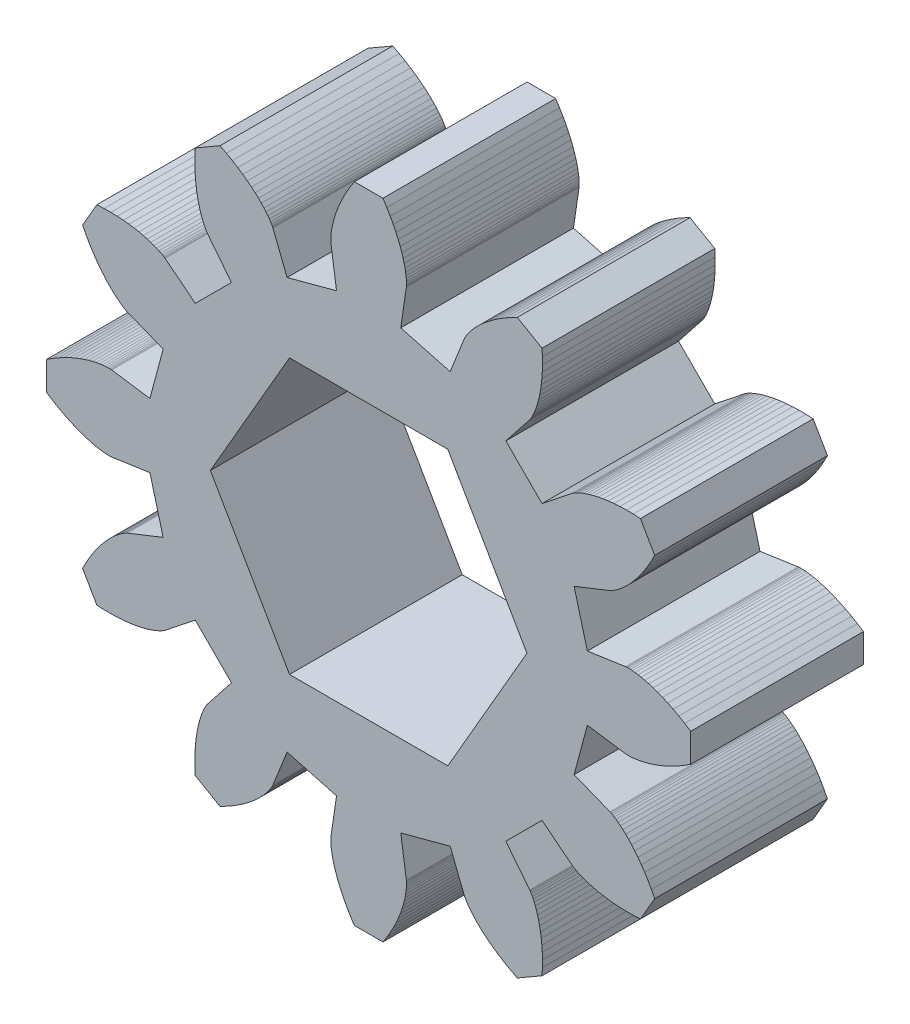
SolidWorks part; units mm, degrees
ref_plane "Front Plane" through (0, 0, 0) normal (0, 0, 1) x (1, 0, 0)
ref_plane "Top Plane" through (0, 0, 0) normal (0, 1, 0) x (1, 0, 0)
ref_plane "Right Plane" through (0, 0, 0) normal (1, 0, 0) x (0, 0, -1)
sketch "Model" plane through (0, 0, 0) normal (0, 0, 1) x (1, 0, 0)
  line L0 (7.5985, 1.1158) -> (8.9253, 1.3107)
  line L1 (8.9253, 1.3107) -> (8.932, 1.3115)
  line L2 (8.932, 1.3115) -> (8.9523, 1.3132)
  line L3 (8.9523, 1.3132) -> (8.986, 1.3148)
  line L4 (8.986, 1.3148) -> (9.0334, 1.3152)
  line L5 (9.0334, 1.3152) -> (9.0943, 1.3135)
  line L6 (9.0943, 1.3135) -> (9.1685, 1.3084)
  line L7 (9.1685, 1.3084) -> (9.2559, 1.2991)
  line L8 (9.2559, 1.2991) -> (9.3563, 1.2844)
  line L9 (9.3563, 1.2844) -> (9.4694, 1.2634)
  line L10 (9.4694, 1.2634) -> (9.5947, 1.2351)
  line L11 (9.5947, 1.2351) -> (9.732, 1.1984)
  line L12 (9.732, 1.1984) -> (9.8806, 1.1524)
  line L13 (9.8806, 1.1524) -> (10.0401, 1.0963)
  line L14 (10.0401, 1.0963) -> (10.2099, 1.029)
  line L15 (10.2099, 1.029) -> (10.3894, 0.9497)
  line L16 (10.3894, 0.9497) -> (10.5778, 0.8576)
  line L17 (10.5778, 0.8576) -> (10.7744, 0.7519)
  line L18 (10.7744, 0.7519) -> (10.9784, 0.6318)
  line L19 (10.9784, 0.6318) -> (11.189, 0.4965)
  line L20 (11.189, 0.4965) -> (11.189, -0.4965)
  line L21 (11.189, -0.4965) -> (10.9784, -0.6318)
  line L22 (10.9784, -0.6318) -> (10.7744, -0.7519)
  line L23 (10.7744, -0.7519) -> (10.5778, -0.8576)
  line L24 (10.5778, -0.8576) -> (10.3894, -0.9497)
  line L25 (10.3894, -0.9497) -> (10.2099, -1.029)
  line L26 (10.2099, -1.029) -> (10.0401, -1.0963)
  line L27 (10.0401, -1.0963) -> (9.8806, -1.1524)
  line L28 (9.8806, -1.1524) -> (9.732, -1.1984)
  line L29 (9.732, -1.1984) -> (9.5947, -1.2351)
  line L30 (9.5947, -1.2351) -> (9.4694, -1.2634)
  line L31 (9.4694, -1.2634) -> (9.3563, -1.2844)
  line L32 (9.3563, -1.2844) -> (9.2559, -1.2991)
  line L33 (9.2559, -1.2991) -> (9.1685, -1.3084)
  line L34 (9.1685, -1.3084) -> (9.0943, -1.3135)
  line L35 (9.0943, -1.3135) -> (9.0334, -1.3152)
  line L36 (9.0334, -1.3152) -> (8.986, -1.3148)
  line L37 (8.986, -1.3148) -> (8.9523, -1.3132)
  line L38 (8.9523, -1.3132) -> (8.932, -1.3115)
  line L39 (8.932, -1.3115) -> (8.9253, -1.3107)
  line L40 (8.9253, -1.3107) -> (7.5985, -1.1158)
  line L41 (7.5985, -1.1158) -> (7.1384, -2.8329)
  line L42 (7.1384, -2.8329) -> (8.3849, -3.3276)
  line L43 (8.3849, -3.3276) -> (8.3911, -3.3303)
  line L44 (8.3911, -3.3303) -> (8.4095, -3.3389)
  line L45 (8.4095, -3.3389) -> (8.4396, -3.3544)
  line L46 (8.4396, -3.3544) -> (8.4808, -3.3777)
  line L47 (8.4808, -3.3777) -> (8.5326, -3.4096)
  line L48 (8.5326, -3.4096) -> (8.5944, -3.4511)
  line L49 (8.5944, -3.4511) -> (8.6654, -3.5029)
  line L50 (8.6654, -3.5029) -> (8.745, -3.5658)
  line L51 (8.745, -3.5658) -> (8.8324, -3.6406)
  line L52 (8.8324, -3.6406) -> (8.9268, -3.7278)
  line L53 (8.9268, -3.7278) -> (9.0273, -3.8282)
  line L54 (9.0273, -3.8282) -> (9.1331, -3.9423)
  line L55 (9.1331, -3.9423) -> (9.2431, -4.0707)
  line L56 (9.2431, -4.0707) -> (9.3566, -4.2138)
  line L57 (9.3566, -4.2138) -> (9.4723, -4.3722)
  line L58 (9.4723, -4.3722) -> (9.5894, -4.5462)
  line L59 (9.5894, -4.5462) -> (9.7068, -4.736)
  line L60 (9.7068, -4.736) -> (9.8235, -4.9421)
  line L61 (9.8235, -4.9421) -> (9.9382, -5.1645)
  line L62 (9.9382, -5.1645) -> (9.4417, -6.0245)
  line L63 (9.4417, -6.0245) -> (9.1917, -6.0363)
  line L64 (9.1917, -6.0363) -> (8.9549, -6.0384)
  line L65 (8.9549, -6.0384) -> (8.7318, -6.0316)
  line L66 (8.7318, -6.0316) -> (8.5226, -6.0172)
  line L67 (8.5226, -6.0172) -> (8.3276, -5.9961)
  line L68 (8.3276, -5.9961) -> (8.1469, -5.9695)
  line L69 (8.1469, -5.9695) -> (7.9807, -5.9383)
  line L70 (7.9807, -5.9383) -> (7.829, -5.9038)
  line L71 (7.829, -5.9038) -> (7.6918, -5.867)
  line L72 (7.6918, -5.867) -> (7.569, -5.8288)
  line L73 (7.569, -5.8288) -> (7.4606, -5.7905)
  line L74 (7.4606, -5.7905) -> (7.3663, -5.753)
  line L75 (7.3663, -5.753) -> (7.2859, -5.7174)
  line L76 (7.2859, -5.7174) -> (7.2191, -5.6846)
  line L77 (7.2191, -5.6846) -> (7.1655, -5.6557)
  line L78 (7.1655, -5.6557) -> (7.1247, -5.6317)
  line L79 (7.1247, -5.6317) -> (7.0963, -5.6134)
  line L80 (7.0963, -5.6134) -> (7.0796, -5.6018)
  line L81 (7.0796, -5.6018) -> (7.0742, -5.5977)
  line L82 (7.0742, -5.5977) -> (6.0226, -4.7656)
  line L83 (6.0226, -4.7656) -> (4.7656, -6.0226)
  line L84 (4.7656, -6.0226) -> (5.5977, -7.0742)
  line L85 (5.5977, -7.0742) -> (5.6018, -7.0796)
  line L86 (5.6018, -7.0796) -> (5.6134, -7.0963)
  line L87 (5.6134, -7.0963) -> (5.6317, -7.1247)
  line L88 (5.6317, -7.1247) -> (5.6557, -7.1655)
  line L89 (5.6557, -7.1655) -> (5.6846, -7.2191)
  line L90 (5.6846, -7.2191) -> (5.7174, -7.2859)
  line L91 (5.7174, -7.2859) -> (5.753, -7.3663)
  line L92 (5.753, -7.3663) -> (5.7905, -7.4606)
  line L93 (5.7905, -7.4606) -> (5.8288, -7.569)
  line L94 (5.8288, -7.569) -> (5.867, -7.6918)
  line L95 (5.867, -7.6918) -> (5.9038, -7.829)
  line L96 (5.9038, -7.829) -> (5.9383, -7.9807)
  line L97 (5.9383, -7.9807) -> (5.9695, -8.1469)
  line L98 (5.9695, -8.1469) -> (5.9961, -8.3276)
  line L99 (5.9961, -8.3276) -> (6.0172, -8.5226)
  line L100 (6.0172, -8.5226) -> (6.0316, -8.7318)
  line L101 (6.0316, -8.7318) -> (6.0384, -8.9549)
  line L102 (6.0384, -8.9549) -> (6.0363, -9.1917)
  line L103 (6.0363, -9.1917) -> (6.0245, -9.4417)
  line L104 (6.0245, -9.4417) -> (5.1645, -9.9382)
  line L105 (5.1645, -9.9382) -> (4.9421, -9.8235)
  line L106 (4.9421, -9.8235) -> (4.736, -9.7068)
  line L107 (4.736, -9.7068) -> (4.5462, -9.5894)
  line L108 (4.5462, -9.5894) -> (4.3722, -9.4723)
  line L109 (4.3722, -9.4723) -> (4.2138, -9.3566)
  line L110 (4.2138, -9.3566) -> (4.0707, -9.2431)
  line L111 (4.0707, -9.2431) -> (3.9423, -9.1331)
  line L112 (3.9423, -9.1331) -> (3.8282, -9.0273)
  line L113 (3.8282, -9.0273) -> (3.7278, -8.9268)
  line L114 (3.7278, -8.9268) -> (3.6406, -8.8324)
  line L115 (3.6406, -8.8324) -> (3.5658, -8.745)
  line L116 (3.5658, -8.745) -> (3.5029, -8.6654)
  line L117 (3.5029, -8.6654) -> (3.4511, -8.5944)
  line L118 (3.4511, -8.5944) -> (3.4096, -8.5326)
  line L119 (3.4096, -8.5326) -> (3.3777, -8.4808)
  line L120 (3.3777, -8.4808) -> (3.3544, -8.4396)
  line L121 (3.3544, -8.4396) -> (3.3389, -8.4095)
  line L122 (3.3389, -8.4095) -> (3.3303, -8.3911)
  line L123 (3.3303, -8.3911) -> (3.3276, -8.3849)
  line L124 (3.3276, -8.3849) -> (2.8329, -7.1384)
  line L125 (2.8329, -7.1384) -> (1.1158, -7.5985)
  line L126 (1.1158, -7.5985) -> (1.3107, -8.9253)
  line L127 (1.3107, -8.9253) -> (1.3115, -8.932)
  line L128 (1.3115, -8.932) -> (1.3132, -8.9523)
  line L129 (1.3132, -8.9523) -> (1.3148, -8.986)
  line L130 (1.3148, -8.986) -> (1.3152, -9.0334)
  line L131 (1.3152, -9.0334) -> (1.3135, -9.0943)
  line L132 (1.3135, -9.0943) -> (1.3084, -9.1685)
  line L133 (1.3084, -9.1685) -> (1.2991, -9.2559)
  line L134 (1.2991, -9.2559) -> (1.2844, -9.3563)
  line L135 (1.2844, -9.3563) -> (1.2634, -9.4694)
  line L136 (1.2634, -9.4694) -> (1.2351, -9.5947)
  line L137 (1.2351, -9.5947) -> (1.1984, -9.732)
  line L138 (1.1984, -9.732) -> (1.1524, -9.8806)
  line L139 (1.1524, -9.8806) -> (1.0963, -10.0401)
  line L140 (1.0963, -10.0401) -> (1.029, -10.2099)
  line L141 (1.029, -10.2099) -> (0.9497, -10.3894)
  line L142 (0.9497, -10.3894) -> (0.8576, -10.5778)
  line L143 (0.8576, -10.5778) -> (0.7519, -10.7744)
  line L144 (0.7519, -10.7744) -> (0.6318, -10.9784)
  line L145 (0.6318, -10.9784) -> (0.4965, -11.189)
  line L146 (0.4965, -11.189) -> (-0.4965, -11.189)
  line L147 (-0.4965, -11.189) -> (-0.6318, -10.9784)
  line L148 (-0.6318, -10.9784) -> (-0.7519, -10.7744)
  line L149 (-0.7519, -10.7744) -> (-0.8576, -10.5778)
  line L150 (-0.8576, -10.5778) -> (-0.9497, -10.3894)
  line L151 (-0.9497, -10.3894) -> (-1.029, -10.2099)
  line L152 (-1.029, -10.2099) -> (-1.0963, -10.0401)
  line L153 (-1.0963, -10.0401) -> (-1.1524, -9.8806)
  line L154 (-1.1524, -9.8806) -> (-1.1984, -9.732)
  line L155 (-1.1984, -9.732) -> (-1.2351, -9.5947)
  line L156 (-1.2351, -9.5947) -> (-1.2634, -9.4694)
  line L157 (-1.2634, -9.4694) -> (-1.2844, -9.3563)
  line L158 (-1.2844, -9.3563) -> (-1.2991, -9.2559)
  line L159 (-1.2991, -9.2559) -> (-1.3084, -9.1685)
  line L160 (-1.3084, -9.1685) -> (-1.3135, -9.0943)
  line L161 (-1.3135, -9.0943) -> (-1.3152, -9.0334)
  line L162 (-1.3152, -9.0334) -> (-1.3148, -8.986)
  line L163 (-1.3148, -8.986) -> (-1.3132, -8.9523)
  line L164 (-1.3132, -8.9523) -> (-1.3115, -8.932)
  line L165 (-1.3115, -8.932) -> (-1.3107, -8.9253)
  line L166 (-1.3107, -8.9253) -> (-1.1158, -7.5985)
  line L167 (-1.1158, -7.5985) -> (-2.8329, -7.1384)
  line L168 (-2.8329, -7.1384) -> (-3.3276, -8.3849)
  line L169 (-3.3276, -8.3849) -> (-3.3303, -8.3911)
  line L170 (-3.3303, -8.3911) -> (-3.3389, -8.4095)
  line L171 (-3.3389, -8.4095) -> (-3.3544, -8.4396)
  line L172 (-3.3544, -8.4396) -> (-3.3777, -8.4808)
  line L173 (-3.3777, -8.4808) -> (-3.4096, -8.5326)
  line L174 (-3.4096, -8.5326) -> (-3.4511, -8.5944)
  line L175 (-3.4511, -8.5944) -> (-3.5029, -8.6654)
  line L176 (-3.5029, -8.6654) -> (-3.5658, -8.745)
  line L177 (-3.5658, -8.745) -> (-3.6406, -8.8324)
  line L178 (-3.6406, -8.8324) -> (-3.7278, -8.9268)
  line L179 (-3.7278, -8.9268) -> (-3.8282, -9.0273)
  line L180 (-3.8282, -9.0273) -> (-3.9423, -9.1331)
  line L181 (-3.9423, -9.1331) -> (-4.0707, -9.2431)
  line L182 (-4.0707, -9.2431) -> (-4.2138, -9.3566)
  line L183 (-4.2138, -9.3566) -> (-4.3722, -9.4723)
  line L184 (-4.3722, -9.4723) -> (-4.5462, -9.5894)
  line L185 (-4.5462, -9.5894) -> (-4.736, -9.7068)
  line L186 (-4.736, -9.7068) -> (-4.9421, -9.8235)
  line L187 (-4.9421, -9.8235) -> (-5.1645, -9.9382)
  line L188 (-5.1645, -9.9382) -> (-6.0245, -9.4417)
  line L189 (-6.0245, -9.4417) -> (-6.0363, -9.1917)
  line L190 (-6.0363, -9.1917) -> (-6.0384, -8.9549)
  line L191 (-6.0384, -8.9549) -> (-6.0316, -8.7318)
  line L192 (-6.0316, -8.7318) -> (-6.0172, -8.5226)
  line L193 (-6.0172, -8.5226) -> (-5.9961, -8.3276)
  line L194 (-5.9961, -8.3276) -> (-5.9695, -8.1469)
  line L195 (-5.9695, -8.1469) -> (-5.9383, -7.9807)
  line L196 (-5.9383, -7.9807) -> (-5.9038, -7.829)
  line L197 (-5.9038, -7.829) -> (-5.867, -7.6918)
  line L198 (-5.867, -7.6918) -> (-5.8288, -7.569)
  line L199 (-5.8288, -7.569) -> (-5.7905, -7.4606)
  line L200 (-5.7905, -7.4606) -> (-5.753, -7.3663)
  line L201 (-5.753, -7.3663) -> (-5.7174, -7.2859)
  line L202 (-5.7174, -7.2859) -> (-5.6846, -7.2191)
  line L203 (-5.6846, -7.2191) -> (-5.6557, -7.1655)
  line L204 (-5.6557, -7.1655) -> (-5.6317, -7.1247)
  line L205 (-5.6317, -7.1247) -> (-5.6134, -7.0963)
  line L206 (-5.6134, -7.0963) -> (-5.6018, -7.0796)
  line L207 (-5.6018, -7.0796) -> (-5.5977, -7.0742)
  line L208 (-5.5977, -7.0742) -> (-4.7656, -6.0226)
  line L209 (-4.7656, -6.0226) -> (-6.0226, -4.7656)
  line L210 (-6.0226, -4.7656) -> (-7.0742, -5.5977)
  line L211 (-7.0742, -5.5977) -> (-7.0796, -5.6018)
  line L212 (-7.0796, -5.6018) -> (-7.0963, -5.6134)
  line L213 (-7.0963, -5.6134) -> (-7.1247, -5.6317)
  line L214 (-7.1247, -5.6317) -> (-7.1655, -5.6557)
  line L215 (-7.1655, -5.6557) -> (-7.2191, -5.6846)
  line L216 (-7.2191, -5.6846) -> (-7.2859, -5.7174)
  line L217 (-7.2859, -5.7174) -> (-7.3663, -5.753)
  line L218 (-7.3663, -5.753) -> (-7.4606, -5.7905)
  line L219 (-7.4606, -5.7905) -> (-7.569, -5.8288)
  line L220 (-7.569, -5.8288) -> (-7.6918, -5.867)
  line L221 (-7.6918, -5.867) -> (-7.829, -5.9038)
  line L222 (-7.829, -5.9038) -> (-7.9807, -5.9383)
  line L223 (-7.9807, -5.9383) -> (-8.1469, -5.9695)
  line L224 (-8.1469, -5.9695) -> (-8.3276, -5.9961)
  line L225 (-8.3276, -5.9961) -> (-8.5226, -6.0172)
  line L226 (-8.5226, -6.0172) -> (-8.7318, -6.0316)
  line L227 (-8.7318, -6.0316) -> (-8.9549, -6.0384)
  line L228 (-8.9549, -6.0384) -> (-9.1917, -6.0363)
  line L229 (-9.1917, -6.0363) -> (-9.4417, -6.0245)
  line L230 (-9.4417, -6.0245) -> (-9.9382, -5.1645)
  line L231 (-9.9382, -5.1645) -> (-9.8235, -4.9421)
  line L232 (-9.8235, -4.9421) -> (-9.7068, -4.736)
  line L233 (-9.7068, -4.736) -> (-9.5894, -4.5462)
  line L234 (-9.5894, -4.5462) -> (-9.4723, -4.3722)
  line L235 (-9.4723, -4.3722) -> (-9.3566, -4.2138)
  line L236 (-9.3566, -4.2138) -> (-9.2431, -4.0707)
  line L237 (-9.2431, -4.0707) -> (-9.1331, -3.9423)
  line L238 (-9.1331, -3.9423) -> (-9.0273, -3.8282)
  line L239 (-9.0273, -3.8282) -> (-8.9268, -3.7278)
  line L240 (-8.9268, -3.7278) -> (-8.8324, -3.6406)
  line L241 (-8.8324, -3.6406) -> (-8.745, -3.5658)
  line L242 (-8.745, -3.5658) -> (-8.6654, -3.5029)
  line L243 (-8.6654, -3.5029) -> (-8.5944, -3.4511)
  line L244 (-8.5944, -3.4511) -> (-8.5326, -3.4096)
  line L245 (-8.5326, -3.4096) -> (-8.4808, -3.3777)
  line L246 (-8.4808, -3.3777) -> (-8.4396, -3.3544)
  line L247 (-8.4396, -3.3544) -> (-8.4095, -3.3389)
  line L248 (-8.4095, -3.3389) -> (-8.3911, -3.3303)
  line L249 (-8.3911, -3.3303) -> (-8.3849, -3.3276)
  line L250 (-8.3849, -3.3276) -> (-7.1384, -2.8329)
  line L251 (-7.1384, -2.8329) -> (-7.5985, -1.1158)
  line L252 (-7.5985, -1.1158) -> (-8.9253, -1.3107)
  line L253 (-8.9253, -1.3107) -> (-8.932, -1.3115)
  line L254 (-8.932, -1.3115) -> (-8.9523, -1.3132)
  line L255 (-8.9523, -1.3132) -> (-8.986, -1.3148)
  line L256 (-8.986, -1.3148) -> (-9.0334, -1.3152)
  line L257 (-9.0334, -1.3152) -> (-9.0943, -1.3135)
  line L258 (-9.0943, -1.3135) -> (-9.1685, -1.3084)
  line L259 (-9.1685, -1.3084) -> (-9.2559, -1.2991)
  line L260 (-9.2559, -1.2991) -> (-9.3563, -1.2844)
  line L261 (-9.3563, -1.2844) -> (-9.4694, -1.2634)
  line L262 (-9.4694, -1.2634) -> (-9.5947, -1.2351)
  line L263 (-9.5947, -1.2351) -> (-9.732, -1.1984)
  line L264 (-9.732, -1.1984) -> (-9.8806, -1.1524)
  line L265 (-9.8806, -1.1524) -> (-10.0401, -1.0963)
  line L266 (-10.0401, -1.0963) -> (-10.2099, -1.029)
  line L267 (-10.2099, -1.029) -> (-10.3894, -0.9497)
  line L268 (-10.3894, -0.9497) -> (-10.5778, -0.8576)
  line L269 (-10.5778, -0.8576) -> (-10.7744, -0.7519)
  line L270 (-10.7744, -0.7519) -> (-10.9784, -0.6318)
  line L271 (-10.9784, -0.6318) -> (-11.189, -0.4965)
  line L272 (-11.189, -0.4965) -> (-11.189, 0.4965)
  line L273 (-11.189, 0.4965) -> (-10.9784, 0.6318)
  line L274 (-10.9784, 0.6318) -> (-10.7744, 0.7519)
  line L275 (-10.7744, 0.7519) -> (-10.5778, 0.8576)
  line L276 (-10.5778, 0.8576) -> (-10.3894, 0.9497)
  line L277 (-10.3894, 0.9497) -> (-10.2099, 1.029)
  line L278 (-10.2099, 1.029) -> (-10.0401, 1.0963)
  line L279 (-10.0401, 1.0963) -> (-9.8806, 1.1524)
  line L280 (-9.8806, 1.1524) -> (-9.732, 1.1984)
  line L281 (-9.732, 1.1984) -> (-9.5947, 1.2351)
  line L282 (-9.5947, 1.2351) -> (-9.4694, 1.2634)
  line L283 (-9.4694, 1.2634) -> (-9.3563, 1.2844)
  line L284 (-9.3563, 1.2844) -> (-9.2559, 1.2991)
  line L285 (-9.2559, 1.2991) -> (-9.1685, 1.3084)
  line L286 (-9.1685, 1.3084) -> (-9.0943, 1.3135)
  line L287 (-9.0943, 1.3135) -> (-9.0334, 1.3152)
  line L288 (-9.0334, 1.3152) -> (-8.986, 1.3148)
  line L289 (-8.986, 1.3148) -> (-8.9523, 1.3132)
  line L290 (-8.9523, 1.3132) -> (-8.932, 1.3115)
  line L291 (-8.932, 1.3115) -> (-8.9253, 1.3107)
  line L292 (-8.9253, 1.3107) -> (-7.5985, 1.1158)
  line L293 (-7.5985, 1.1158) -> (-7.1384, 2.8329)
  line L294 (-7.1384, 2.8329) -> (-8.3849, 3.3276)
  line L295 (-8.3849, 3.3276) -> (-8.3911, 3.3303)
  line L296 (-8.3911, 3.3303) -> (-8.4095, 3.3389)
  line L297 (-8.4095, 3.3389) -> (-8.4396, 3.3544)
  line L298 (-8.4396, 3.3544) -> (-8.4808, 3.3777)
  line L299 (-8.4808, 3.3777) -> (-8.5326, 3.4096)
  line L300 (-8.5326, 3.4096) -> (-8.5944, 3.4511)
  line L301 (-8.5944, 3.4511) -> (-8.6654, 3.5029)
  line L302 (-8.6654, 3.5029) -> (-8.745, 3.5658)
  line L303 (-8.745, 3.5658) -> (-8.8324, 3.6406)
  line L304 (-8.8324, 3.6406) -> (-8.9268, 3.7278)
  line L305 (-8.9268, 3.7278) -> (-9.0273, 3.8282)
  line L306 (-9.0273, 3.8282) -> (-9.1331, 3.9423)
  line L307 (-9.1331, 3.9423) -> (-9.2431, 4.0707)
  line L308 (-9.2431, 4.0707) -> (-9.3566, 4.2138)
  line L309 (-9.3566, 4.2138) -> (-9.4723, 4.3722)
  line L310 (-9.4723, 4.3722) -> (-9.5894, 4.5462)
  line L311 (-9.5894, 4.5462) -> (-9.7068, 4.736)
  line L312 (-9.7068, 4.736) -> (-9.8235, 4.9421)
  line L313 (-9.8235, 4.9421) -> (-9.9382, 5.1645)
  line L314 (-9.9382, 5.1645) -> (-9.4417, 6.0245)
  line L315 (-9.4417, 6.0245) -> (-9.1917, 6.0363)
  line L316 (-9.1917, 6.0363) -> (-8.9549, 6.0384)
  line L317 (-8.9549, 6.0384) -> (-8.7318, 6.0316)
  line L318 (-8.7318, 6.0316) -> (-8.5226, 6.0172)
  line L319 (-8.5226, 6.0172) -> (-8.3276, 5.9961)
  line L320 (-8.3276, 5.9961) -> (-8.1469, 5.9695)
  line L321 (-8.1469, 5.9695) -> (-7.9807, 5.9383)
  line L322 (-7.9807, 5.9383) -> (-7.829, 5.9038)
  line L323 (-7.829, 5.9038) -> (-7.6918, 5.867)
  line L324 (-7.6918, 5.867) -> (-7.569, 5.8288)
  line L325 (-7.569, 5.8288) -> (-7.4606, 5.7905)
  line L326 (-7.4606, 5.7905) -> (-7.3663, 5.753)
  line L327 (-7.3663, 5.753) -> (-7.2859, 5.7174)
  line L328 (-7.2859, 5.7174) -> (-7.2191, 5.6846)
  line L329 (-7.2191, 5.6846) -> (-7.1655, 5.6557)
  line L330 (-7.1655, 5.6557) -> (-7.1247, 5.6317)
  line L331 (-7.1247, 5.6317) -> (-7.0963, 5.6134)
  line L332 (-7.0963, 5.6134) -> (-7.0796, 5.6018)
  line L333 (-7.0796, 5.6018) -> (-7.0742, 5.5977)
  line L334 (-7.0742, 5.5977) -> (-6.0226, 4.7656)
  line L335 (-6.0226, 4.7656) -> (-4.7656, 6.0226)
  line L336 (-4.7656, 6.0226) -> (-5.5977, 7.0742)
  line L337 (-5.5977, 7.0742) -> (-5.6018, 7.0796)
  line L338 (-5.6018, 7.0796) -> (-5.6134, 7.0963)
  line L339 (-5.6134, 7.0963) -> (-5.6317, 7.1247)
  line L340 (-5.6317, 7.1247) -> (-5.6557, 7.1655)
  line L341 (-5.6557, 7.1655) -> (-5.6846, 7.2191)
  line L342 (-5.6846, 7.2191) -> (-5.7174, 7.2859)
  line L343 (-5.7174, 7.2859) -> (-5.753, 7.3663)
  line L344 (-5.753, 7.3663) -> (-5.7905, 7.4606)
  line L345 (-5.7905, 7.4606) -> (-5.8288, 7.569)
  line L346 (-5.8288, 7.569) -> (-5.867, 7.6918)
  line L347 (-5.867, 7.6918) -> (-5.9038, 7.829)
  line L348 (-5.9038, 7.829) -> (-5.9383, 7.9807)
  line L349 (-5.9383, 7.9807) -> (-5.9695, 8.1469)
  line L350 (-5.9695, 8.1469) -> (-5.9961, 8.3276)
  line L351 (-5.9961, 8.3276) -> (-6.0172, 8.5226)
  line L352 (-6.0172, 8.5226) -> (-6.0316, 8.7318)
  line L353 (-6.0316, 8.7318) -> (-6.0384, 8.9549)
  line L354 (-6.0384, 8.9549) -> (-6.0363, 9.1917)
  line L355 (-6.0363, 9.1917) -> (-6.0245, 9.4417)
  line L356 (-6.0245, 9.4417) -> (-5.1645, 9.9382)
  line L357 (-5.1645, 9.9382) -> (-4.9421, 9.8235)
  line L358 (-4.9421, 9.8235) -> (-4.736, 9.7068)
  line L359 (-4.736, 9.7068) -> (-4.5462, 9.5894)
  line L360 (-4.5462, 9.5894) -> (-4.3722, 9.4723)
  line L361 (-4.3722, 9.4723) -> (-4.2138, 9.3566)
  line L362 (-4.2138, 9.3566) -> (-4.0707, 9.2431)
  line L363 (-4.0707, 9.2431) -> (-3.9423, 9.1331)
  line L364 (-3.9423, 9.1331) -> (-3.8282, 9.0273)
  line L365 (-3.8282, 9.0273) -> (-3.7278, 8.9268)
  line L366 (-3.7278, 8.9268) -> (-3.6406, 8.8324)
  line L367 (-3.6406, 8.8324) -> (-3.5658, 8.745)
  line L368 (-3.5658, 8.745) -> (-3.5029, 8.6654)
  line L369 (-3.5029, 8.6654) -> (-3.4511, 8.5944)
  line L370 (-3.4511, 8.5944) -> (-3.4096, 8.5326)
  line L371 (-3.4096, 8.5326) -> (-3.3777, 8.4808)
  line L372 (-3.3777, 8.4808) -> (-3.3544, 8.4396)
  line L373 (-3.3544, 8.4396) -> (-3.3389, 8.4095)
  line L374 (-3.3389, 8.4095) -> (-3.3303, 8.3911)
  line L375 (-3.3303, 8.3911) -> (-3.3276, 8.3849)
  line L376 (-3.3276, 8.3849) -> (-2.8329, 7.1384)
  line L377 (-2.8329, 7.1384) -> (-1.1158, 7.5985)
  line L378 (-1.1158, 7.5985) -> (-1.3107, 8.9253)
  line L379 (-1.3107, 8.9253) -> (-1.3115, 8.932)
  line L380 (-1.3115, 8.932) -> (-1.3132, 8.9523)
  line L381 (-1.3132, 8.9523) -> (-1.3148, 8.986)
  line L382 (-1.3148, 8.986) -> (-1.3152, 9.0334)
  line L383 (-1.3152, 9.0334) -> (-1.3135, 9.0943)
  line L384 (-1.3135, 9.0943) -> (-1.3084, 9.1685)
  line L385 (-1.3084, 9.1685) -> (-1.2991, 9.2559)
  line L386 (-1.2991, 9.2559) -> (-1.2844, 9.3563)
  line L387 (-1.2844, 9.3563) -> (-1.2634, 9.4694)
  line L388 (-1.2634, 9.4694) -> (-1.2351, 9.5947)
  line L389 (-1.2351, 9.5947) -> (-1.1984, 9.732)
  line L390 (-1.1984, 9.732) -> (-1.1524, 9.8806)
  line L391 (-1.1524, 9.8806) -> (-1.0963, 10.0401)
  line L392 (-1.0963, 10.0401) -> (-1.029, 10.2099)
  line L393 (-1.029, 10.2099) -> (-0.9497, 10.3894)
  line L394 (-0.9497, 10.3894) -> (-0.8576, 10.5778)
  line L395 (-0.8576, 10.5778) -> (-0.7519, 10.7744)
  line L396 (-0.7519, 10.7744) -> (-0.6318, 10.9784)
  line L397 (-0.6318, 10.9784) -> (-0.4965, 11.189)
  line L398 (-0.4965, 11.189) -> (0.4965, 11.189)
  line L399 (0.4965, 11.189) -> (0.6318, 10.9784)
  line L400 (0.6318, 10.9784) -> (0.7519, 10.7744)
  line L401 (0.7519, 10.7744) -> (0.8576, 10.5778)
  line L402 (0.8576, 10.5778) -> (0.9497, 10.3894)
  line L403 (0.9497, 10.3894) -> (1.029, 10.2099)
  line L404 (1.029, 10.2099) -> (1.0963, 10.0401)
  line L405 (1.0963, 10.0401) -> (1.1524, 9.8806)
  line L406 (1.1524, 9.8806) -> (1.1984, 9.732)
  line L407 (1.1984, 9.732) -> (1.2351, 9.5947)
  line L408 (1.2351, 9.5947) -> (1.2634, 9.4694)
  line L409 (1.2634, 9.4694) -> (1.2844, 9.3563)
  line L410 (1.2844, 9.3563) -> (1.2991, 9.2559)
  line L411 (1.2991, 9.2559) -> (1.3084, 9.1685)
  line L412 (1.3084, 9.1685) -> (1.3135, 9.0943)
  line L413 (1.3135, 9.0943) -> (1.3152, 9.0334)
  line L414 (1.3152, 9.0334) -> (1.3148, 8.986)
  line L415 (1.3148, 8.986) -> (1.3132, 8.9523)
  line L416 (1.3132, 8.9523) -> (1.3115, 8.932)
  line L417 (1.3115, 8.932) -> (1.3107, 8.9253)
  line L418 (1.3107, 8.9253) -> (1.1158, 7.5985)
  line L419 (1.1158, 7.5985) -> (2.8329, 7.1384)
  line L420 (2.8329, 7.1384) -> (3.3276, 8.3849)
  line L421 (3.3276, 8.3849) -> (3.3303, 8.3911)
  line L422 (3.3303, 8.3911) -> (3.3389, 8.4095)
  line L423 (3.3389, 8.4095) -> (3.3544, 8.4396)
  line L424 (3.3544, 8.4396) -> (3.3777, 8.4808)
  line L425 (3.3777, 8.4808) -> (3.4096, 8.5326)
  line L426 (3.4096, 8.5326) -> (3.4511, 8.5944)
  line L427 (3.4511, 8.5944) -> (3.5029, 8.6654)
  line L428 (3.5029, 8.6654) -> (3.5658, 8.745)
  line L429 (3.5658, 8.745) -> (3.6406, 8.8324)
  line L430 (3.6406, 8.8324) -> (3.7278, 8.9268)
  line L431 (3.7278, 8.9268) -> (3.8282, 9.0273)
  line L432 (3.8282, 9.0273) -> (3.9423, 9.1331)
  line L433 (3.9423, 9.1331) -> (4.0707, 9.2431)
  line L434 (4.0707, 9.2431) -> (4.2138, 9.3566)
  line L435 (4.2138, 9.3566) -> (4.3722, 9.4723)
  line L436 (4.3722, 9.4723) -> (4.5462, 9.5894)
  line L437 (4.5462, 9.5894) -> (4.736, 9.7068)
  line L438 (4.736, 9.7068) -> (4.9421, 9.8235)
  line L439 (4.9421, 9.8235) -> (5.1645, 9.9382)
  line L440 (5.1645, 9.9382) -> (6.0245, 9.4417)
  line L441 (6.0245, 9.4417) -> (6.0363, 9.1917)
  line L442 (6.0363, 9.1917) -> (6.0384, 8.9549)
  line L443 (6.0384, 8.9549) -> (6.0316, 8.7318)
  line L444 (6.0316, 8.7318) -> (6.0172, 8.5226)
  line L445 (6.0172, 8.5226) -> (5.9961, 8.3276)
  line L446 (5.9961, 8.3276) -> (5.9695, 8.1469)
  line L447 (5.9695, 8.1469) -> (5.9383, 7.9807)
  line L448 (5.9383, 7.9807) -> (5.9038, 7.829)
  line L449 (5.9038, 7.829) -> (5.867, 7.6918)
  line L450 (5.867, 7.6918) -> (5.8288, 7.569)
  line L451 (5.8288, 7.569) -> (5.7905, 7.4606)
  line L452 (5.7905, 7.4606) -> (5.753, 7.3663)
  line L453 (5.753, 7.3663) -> (5.7174, 7.2859)
  line L454 (5.7174, 7.2859) -> (5.6846, 7.2191)
  line L455 (5.6846, 7.2191) -> (5.6557, 7.1655)
  line L456 (5.6557, 7.1655) -> (5.6317, 7.1247)
  line L457 (5.6317, 7.1247) -> (5.6134, 7.0963)
  line L458 (5.6134, 7.0963) -> (5.6018, 7.0796)
  line L459 (5.6018, 7.0796) -> (5.5977, 7.0742)
  line L460 (5.5977, 7.0742) -> (4.7656, 6.0226)
  line L461 (4.7656, 6.0226) -> (6.0226, 4.7656)
  line L462 (6.0226, 4.7656) -> (7.0742, 5.5977)
  line L463 (7.0742, 5.5977) -> (7.0796, 5.6018)
  line L464 (7.0796, 5.6018) -> (7.0963, 5.6134)
  line L465 (7.0963, 5.6134) -> (7.1247, 5.6317)
  line L466 (7.1247, 5.6317) -> (7.1655, 5.6557)
  line L467 (7.1655, 5.6557) -> (7.2191, 5.6846)
  line L468 (7.2191, 5.6846) -> (7.2859, 5.7174)
  line L469 (7.2859, 5.7174) -> (7.3663, 5.753)
  line L470 (7.3663, 5.753) -> (7.4606, 5.7905)
  line L471 (7.4606, 5.7905) -> (7.569, 5.8288)
  line L472 (7.569, 5.8288) -> (7.6918, 5.867)
  line L473 (7.6918, 5.867) -> (7.829, 5.9038)
  line L474 (7.829, 5.9038) -> (7.9807, 5.9383)
  line L475 (7.9807, 5.9383) -> (8.1469, 5.9695)
  line L476 (8.1469, 5.9695) -> (8.3276, 5.9961)
  line L477 (8.3276, 5.9961) -> (8.5226, 6.0172)
  line L478 (8.5226, 6.0172) -> (8.7318, 6.0316)
  line L479 (8.7318, 6.0316) -> (8.9549, 6.0384)
  line L480 (8.9549, 6.0384) -> (9.1917, 6.0363)
  line L481 (9.1917, 6.0363) -> (9.4417, 6.0245)
  line L482 (9.4417, 6.0245) -> (9.9382, 5.1645)
  line L483 (9.9382, 5.1645) -> (9.8235, 4.9421)
  line L484 (9.8235, 4.9421) -> (9.7068, 4.736)
  line L485 (9.7068, 4.736) -> (9.5894, 4.5462)
  line L486 (9.5894, 4.5462) -> (9.4723, 4.3722)
  line L487 (9.4723, 4.3722) -> (9.3566, 4.2138)
  line L488 (9.3566, 4.2138) -> (9.2431, 4.0707)
  line L489 (9.2431, 4.0707) -> (9.1331, 3.9423)
  line L490 (9.1331, 3.9423) -> (9.0273, 3.8282)
  line L491 (9.0273, 3.8282) -> (8.9268, 3.7278)
  line L492 (8.9268, 3.7278) -> (8.8324, 3.6406)
  line L493 (8.8324, 3.6406) -> (8.745, 3.5658)
  line L494 (8.745, 3.5658) -> (8.6654, 3.5029)
  line L495 (8.6654, 3.5029) -> (8.5944, 3.4511)
  line L496 (8.5944, 3.4511) -> (8.5326, 3.4096)
  line L497 (8.5326, 3.4096) -> (8.4808, 3.3777)
  line L498 (8.4808, 3.3777) -> (8.4396, 3.3544)
  line L499 (8.4396, 3.3544) -> (8.4095, 3.3389)
  line L500 (8.4095, 3.3389) -> (8.3911, 3.3303)
  line L501 (8.3911, 3.3303) -> (8.3849, 3.3276)
  line L502 (8.3849, 3.3276) -> (7.1384, 2.8329)
  line L503 (7.1384, 2.8329) -> (7.5985, 1.1158)
  line L505 (5.4993, 0) -> (2.7496, 4.7625)
  line L506 (2.7496, 4.7625) -> (-2.7496, 4.7625)
  line L507 (-2.7496, 4.7625) -> (-5.4993, 0)
  line L508 (-5.4993, 0) -> (-2.7496, -4.7625)
  line L509 (-2.7496, -4.7625) -> (2.7496, -4.7625)
  line L510 (2.7496, -4.7625) -> (5.4993, 0)
  circle A0 centre (0, 0) radius 4.7625 construction
  dimension "D2" = 9.525
  dimension "D1" = 7.6284
extrude "Boss-Extrude1" add sketch "Model" along normal mid plane 6
ref_axis "Axis1" through (0, 0, -5.1827) along (0, 0, 1)
